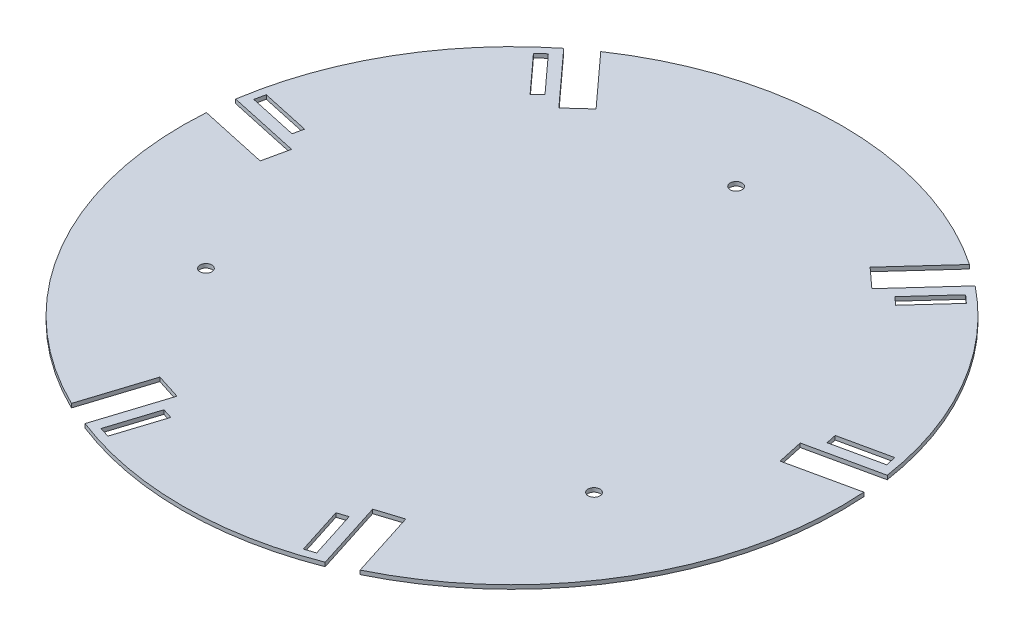
SolidWorks part; units mm, degrees
ref_plane "Front Plane" through (0, 0, 0) normal (0, 0, 1) x (1, 0, 0)
ref_plane "Top Plane" through (0, 0, 0) normal (0, 1, 0) x (1, 0, 0)
ref_plane "Right Plane" through (0, 0, 0) normal (1, 0, 0) x (0, 0, -1)
sketch "Sketch2" plane through (0, 0, 0) normal (0, 1, 0) x (1, 0, 0)
  circle A0 centre (0, 0) radius 125
  dimension "D1" = 250
extrude "Boss-Extrude1" add sketch "Sketch2" along normal blind 1.5 contours A0
sketch "Sketch3" plane through (0, 1.5, 0) normal (0, 1, 0) x (1, 0, 0)
  line L0 (0, 0) -> (-38, -119.084) construction
  line L1 (-270.1917, -358.6733) -> (-267.1917, -358.6733)
  line L2 (-270.1917, -358.6733) -> (-270.1917, -377.6733)
  line L3 (-270.1917, -377.6733) -> (-267.1917, -377.6733)
  line L4 (-267.1917, -358.6733) -> (-267.1917, -377.6733)
  line L9 (-38, -119.084) -> (38, -119.084) construction
  line L10 (0, 0) -> (0, -293.8403) construction
  line L11 (31.312, -98.1252) -> (35.1227, -96.9092)
  line L12 (37.088, -116.226) -> (40.8987, -115.01)
  line L14 (37.088, -116.226) -> (31.312, -98.1252)
  line L15 (40.8987, -115.01) -> (35.1227, -96.9092)
  line L17 (-38, -119.084) -> (-37.088, -116.226) construction
  line L19 (-37.088, -116.226) -> (-31.312, -98.1252)
  line L20 (-37.088, -116.226) -> (-40.8987, -115.01)
  line L21 (-31.312, -98.1252) -> (-35.1227, -96.9092)
  line L22 (-40.8987, -115.01) -> (-35.1227, -96.9092)
  line L52 (-82.1107, 90.2321) -> (-69.3229, 76.1796)
  line L53 (-82.1107, 90.2321) -> (-79.1522, 92.9243)
  line L54 (-79.1522, 92.9243) -> (-66.3645, 78.8717)
  line L55 (-69.3229, 76.1796) -> (-66.3645, 78.8717)
  line L56 (-100.6349, 21.9456) -> (-101.4872, 18.0375)
  line L57 (-120.0509, 22.0857) -> (-101.4872, 18.0375)
  line L58 (-119.1987, 25.9938) -> (-120.0509, 22.0857)
  line L59 (-119.1987, 25.9938) -> (-100.6349, 21.9456)
  line L60 (119.1987, 25.9938) -> (100.6349, 21.9456)
  line L61 (119.1987, 25.9938) -> (120.0509, 22.0857)
  line L62 (120.0509, 22.0857) -> (101.4872, 18.0375)
  line L63 (100.6349, 21.9456) -> (101.4872, 18.0375)
  line L64 (69.3229, 76.1796) -> (66.3645, 78.8717)
  line L65 (79.1522, 92.9243) -> (66.3645, 78.8717)
  line L66 (82.1107, 90.2321) -> (79.1522, 92.9243)
  line L67 (82.1107, 90.2321) -> (69.3229, 76.1796)
  circle A1 centre (0, 0) radius 125 construction
  point P18 (0, 0)
  point P38 (-15.7426, 25.0605)
  point P39 (0, 0)
  point P46 (-7.6333, 12.5317)
  dimension "D1" = 3
  dimension "D2" = 19
  dimension "D3" = 76
  dimension "D4" = 3
  dimension "D5" = 3
  dimension "D7" = 4
  dimension "D8" = 19
extrude "Cut-Extrude1" cut sketch "Sketch3" against normal through all
sketch "Sketch4" plane through (0, 1.5, 0) normal (0, 1, 0) x (1, 0, 0)
  circle A3 centre (0, 85) radius 2.25
  circle A4 centre (73.6122, -42.5) radius 2.25
  circle A5 centre (-73.6122, -42.5) radius 2.25
  point P8 (0, 0)
  dimension "D1" = 85
  dimension "D2" = 3
  dimension "D3" = 4.5
extrude "Cut-Extrude2" cut sketch "Sketch4" against normal through all
sketch "Sketch6" plane through (0, 1.5, 0) normal (0, 1, 0) x (1, 0, 0)
  line L0 (-40.8987, -115.01) -> (-44.7094, -113.794) construction
  line L1 (-35.1227, -96.9092) -> (-40.8987, -115.01) construction
  line L2 (0, 0) -> (0, -140.3527) construction
  line L3 (-44.7094, -113.794) -> (-55.9925, -149.153) construction
  line L4 (-55.9925, -149.153) -> (-65.5193, -146.113)
  line L5 (-55.9925, -149.153) -> (-37.1094, -89.9772)
  line L6 (-65.5193, -146.113) -> (-46.6361, -86.9372)
  line L7 (-37.1094, -89.9772) -> (-46.6361, -86.9372)
  line L8 (65.5193, -146.113) -> (46.6361, -86.9372)
  line L9 (37.1094, -89.9772) -> (46.6361, -86.9372)
  line L10 (55.9925, -149.153) -> (37.1094, -89.9772)
  line L11 (55.9925, -149.153) -> (65.5193, -146.113)
  point P16 (0, 0)
  dimension "D1" = 10
  dimension "D2" = 25
  dimension "D3" = 4
extrude "Cut-Extrude5" cut sketch "Sketch6" against normal through all
pattern_circular "CirPattern2" count 3 over 360 about axis through (0, 1.5, 0) along (0, 1, 0) of "Cut-Extrude5"
